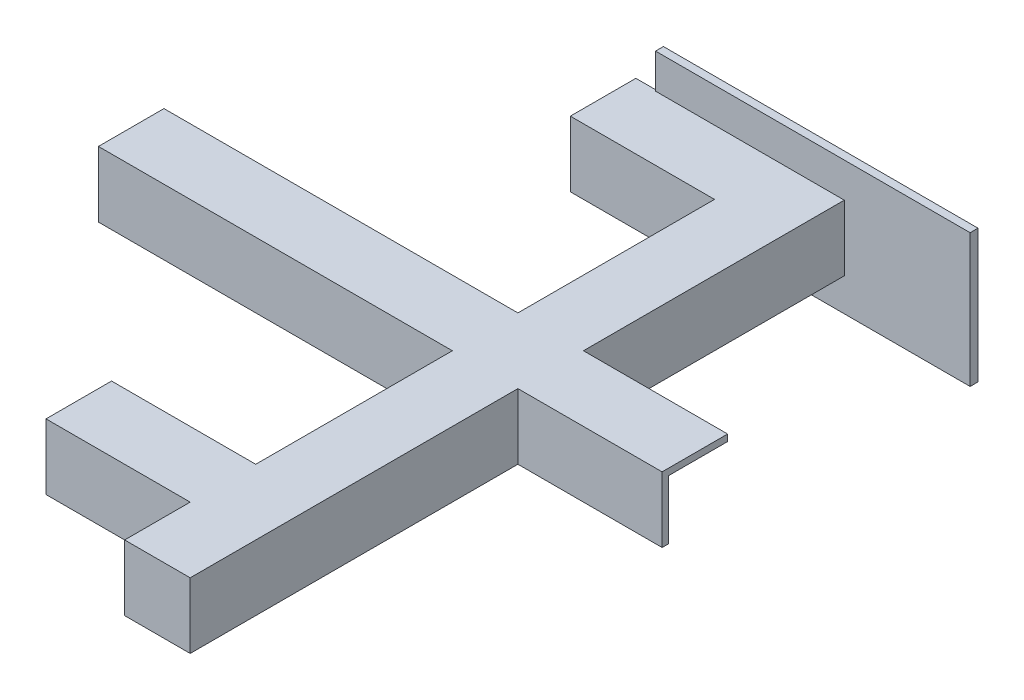
SolidWorks part; units mm, degrees
ref_plane "Plano frontal" through (0, 0, 0) normal (0, 0, 1) x (1, 0, 0)
ref_plane "Plano superior" through (0, 0, 0) normal (0, 1, 0) x (1, 0, 0)
ref_plane "Plano direito" through (0, 0, 0) normal (1, 0, 0) x (0, 0, -1)
sketch "Sketch1" plane through (0, 0, 40212.6002) normal (0, 0, 1) x (1, 0, 0)
  line L0 (-21701.5611, 12327.8571) -> (-21701.5611, -2672.1429) construction
  line L1 (-21550.5611, -1782.1429) -> (-21790.5611, -1782.1429)
  line L2 (-21550.5611, -1782.1429) -> (-21550.5611, -1680.5429)
  line L3 (-21550.5611, -1680.5429) -> (-21790.5611, -1680.5429)
  line L4 (-21790.5611, -1782.1429) -> (-21790.5611, -1680.5429)
  line L5 (-21646.5611, -1707.0357) -> (-21696.5611, -1707.0357)
  line L6 (-21646.5611, -1707.0357) -> (-21646.5611, -1757.0357)
  line L7 (-21646.5611, -1757.0357) -> (-21696.5611, -1757.0357)
  line L8 (-21696.5611, -1707.0357) -> (-21696.5611, -1757.0357)
  line L9 (-21646.5611, -1707.0357) -> (-21696.5611, -1757.0357) construction
  line L10 (-21646.5611, -1757.0357) -> (-21696.5611, -1707.0357) construction
  point P6 (-21671.5611, -1732.0357)
  dimension "D1" = 50
  dimension "D2" = 5
extrude "Boss-Extrude1" add sketch "Sketch1" along normal blind 500 from offset 5 contours L5 L8 L7 L6 region at (-21671.5611, -1732.0357, 40212.6002)
sketch "Sketch2" plane through (-21646.5611, 0, 0) normal (1, 0, 0) x (0, 0, -1)
  line L0 (-40717.6002, -1707.0357) -> (-40217.6002, -1707.0357) construction
  line L1 (-40467.6002, -1757.0357) -> (-40417.6002, -1757.0357)
  line L2 (-40467.6002, -1757.0357) -> (-40467.6002, -1707.0357)
  line L3 (-40467.6002, -1707.0357) -> (-40417.6002, -1707.0357)
  line L4 (-40417.6002, -1757.0357) -> (-40417.6002, -1707.0357)
  line L7 (-40717.6002, -1757.0357) -> (-40217.6002, -1757.0357) construction
  line L8 (-40462.6002, -1757.0357) -> (-40462.6002, -1712.0357)
  line L9 (-40462.6002, -1712.0357) -> (-40417.6002, -1712.0357)
  line L10 (-40217.6002, -1707.0357) -> (-40217.6002, -1757.0357) construction
  line M9 (-40217.6002, -1707.0357) -> (-40717.6002, -1707.0357)
  line M11 (-40717.6002, -1757.0357) -> (-40217.6002, -1757.0357)
  dimension "D1" = 50
  dimension "D2" = 200
  dimension "D3" = 5
extrude "Boss-Extrude2" add sketch "Sketch2" along normal blind 110 contours L8 L9 L4 L2 M9 M11 region at (-21646.5611, -1732.0357, 40466.8931)
sketch "Sketch3" plane through (-21696.5611, 0, 0) normal (-1, 0, 0) x (0, 0, 1)
  line L0 (40717.6002, -1707.0357) -> (40217.6002, -1707.0357) construction
  line L1 (40617.6002, -1707.0357) -> (40667.6002, -1707.0357)
  line L2 (40617.6002, -1707.0357) -> (40617.6002, -1757.0357)
  line L3 (40617.6002, -1757.0357) -> (40667.6002, -1757.0357)
  line L4 (40667.6002, -1707.0357) -> (40667.6002, -1757.0357)
  line L5 (40417.6002, -1707.0357) -> (40467.6002, -1707.0357)
  line L6 (40417.6002, -1707.0357) -> (40417.6002, -1757.0357)
  line L7 (40417.6002, -1757.0357) -> (40467.6002, -1757.0357)
  line L8 (40467.6002, -1707.0357) -> (40467.6002, -1757.0357)
  line L9 (40217.6002, -1707.0357) -> (40267.6002, -1707.0357)
  line L10 (40217.6002, -1707.0357) -> (40217.6002, -1757.0357)
  line L11 (40217.6002, -1757.0357) -> (40267.6002, -1757.0357)
  line L12 (40267.6002, -1707.0357) -> (40267.6002, -1757.0357)
  line L13 (40217.6002, -1707.0357) -> (40217.6002, -1757.0357) construction
  line L15 (40617.6002, -1757.0357) -> (40662.6002, -1757.0357)
  line L16 (40617.6002, -1757.0357) -> (40617.6002, -1712.0357)
  line L17 (40617.6002, -1712.0357) -> (40662.6002, -1712.0357)
  line L18 (40662.6002, -1757.0357) -> (40662.6002, -1712.0357)
  line L19 (40417.6002, -1757.0357) -> (40462.6002, -1757.0357)
  line L20 (40417.6002, -1757.0357) -> (40417.6002, -1712.0357)
  line L21 (40417.6002, -1712.0357) -> (40462.6002, -1712.0357)
  line L22 (40462.6002, -1757.0357) -> (40462.6002, -1712.0357)
  line L23 (40217.6002, -1757.0357) -> (40262.6002, -1757.0357)
  line L24 (40217.6002, -1757.0357) -> (40217.6002, -1712.0357)
  line L25 (40217.6002, -1712.0357) -> (40262.6002, -1712.0357)
  line L26 (40262.6002, -1757.0357) -> (40262.6002, -1712.0357)
  point P25 (40642.6002, -1707.0357)
  line M13 (40217.6002, -1707.0357) -> (40217.6002, -1757.0357)
  line M16 (40717.6002, -1707.0357) -> (40217.6002, -1707.0357)
  dimension "D1" = 50
  dimension "D2" = 400
  dimension "D3" = 200
  dimension "D4" = 5
extrude "Boss-Extrude3" add sketch "Sketch3" along normal blind 110 contours L18 L3 L4 L2 L17 M16 | L22 L7 L8 L6 L21 M16 | L26 L11 L12 L25 M16 M13 region at (-21696.5611, -1707.7428, 40642.6002) region at (-21696.5611, -1732.0357, 40266.8931) region at (-21696.5611, -1732.0357, 40466.8931)
extrude "Boss-Extrude5" add sketch "Sketch3<3>" along normal blind 160 from surface contours L22 L7 L8 L6 L21 M16 region at (-21696.5611, -1732.0357, 40466.8931) starting at face at (-21806.5611, -1725.3691, 40449.2669)
sketch "Sketch3<3>" plane through (-21696.5611, 0, 0) normal (-1, 0, 0) x (0, 0, 1) same geometry as "Sketch3"
extrude "Boss-Extrude6" add sketch "Sketch1<3>" along normal blind 6 contours L3 L4 L1 L2 | L8 L7 L6 L5
sketch "Sketch1<3>" plane through (0, 0, 40212.6002) normal (0, 0, 1) x (1, 0, 0) same geometry as "Sketch1"
